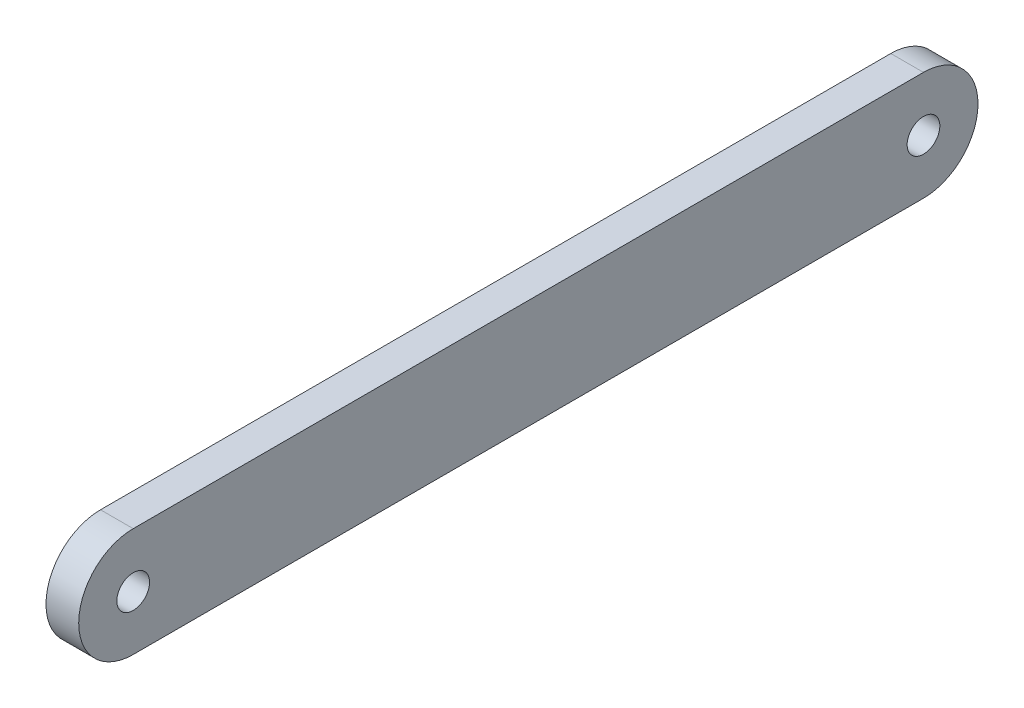
SolidWorks part; units mm, degrees
material "ABS"
ref_plane "Front Plane" through (0, 0, 0) normal (0, 0, 1) x (1, 0, 0)
ref_plane "Top Plane" through (0, 0, 0) normal (0, 1, 0) x (1, 0, 0)
ref_plane "Right Plane" through (0, 0, 0) normal (1, 0, 0) x (0, 0, -1)
sketch "Sketch2" plane through (0, 0, 0) normal (0, 0, 1) x (1, 0, 0)
  line L1 (-1.5, 5) -> (1.5, 5)
  line L2 (-1.5, 5) -> (-1.5, -5)
  line L3 (-1.5, -5) -> (1.5, -5)
  line L4 (1.5, 5) -> (1.5, -5)
  line L5 (-1.5, 5) -> (1.5, -5) construction
  line L6 (-1.5, -5) -> (1.5, 5) construction
  point P0 (0, 0)
extrude "Boss-Extrude1" add sketch "Sketch2" along normal blind 36.25 and the other way blind 36.25
sketch "Sketch3" plane through (0, 0, -36.25) normal (0, 0, -1) x (-1, 0, 0)
  line L0 (1.5, 5) -> (1.5, -5) construction
  line L1 (1.5, 0) -> (-1.5, 0)
  line L2 (1.5, 0) -> (1.5, -5)
  line L3 (1.5, -5) -> (-1.5, -5)
  line L4 (-1.5, 0) -> (-1.5, -5)
revolve "Revolve1" add sketch "Sketch3" angle 360 about L1 region at (0, -2.5, -36.25)
sketch "Sketch4" plane through (1.5, 0, 0) normal (1, 0, 0) x (0, 0, -1)
  circle A0 centre (36.25, 0) radius 1.5
extrude "Cut-Extrude1" cut sketch "Sketch4" against normal up to surface (3 mm away) up to face at (-1.5, 0, -1.25)
mirror "Mirror1" about plane through (0, 0, 0) normal (0, 0, 1) of "Cut-Extrude1", "Revolve1"
ref_plane "Plane1" through (-1.5, 0, 0) normal (-1, 0, 0) x (0, 0, 1)
sketch "Sketch5" plane through (-1.5, 0, 0) normal (-1, 0, 0) x (0, 0, 1)
  line L0 (27.0439, 5) -> (27.0439, -5)
  line L1 (-36.25, 5) -> (36.25, 5) construction
  line L2 (-36.25, -5) -> (36.25, -5) construction
  line L3 (0, 5) -> (0, -5)
  line L4 (-27.0439, 5) -> (-27.0439, -5)
ref_plane "Plane2" through (1.5, 0, 0) normal (1, 0, 0) x (0, 0, -1)
sketch "Sketch6" plane through (1.5, 0, 0) normal (1, 0, 0) x (0, 0, -1)
  line L0 (-27.0439, 5) -> (-27.0439, -5)
  line L1 (27.0439, 5) -> (27.0439, -5)
